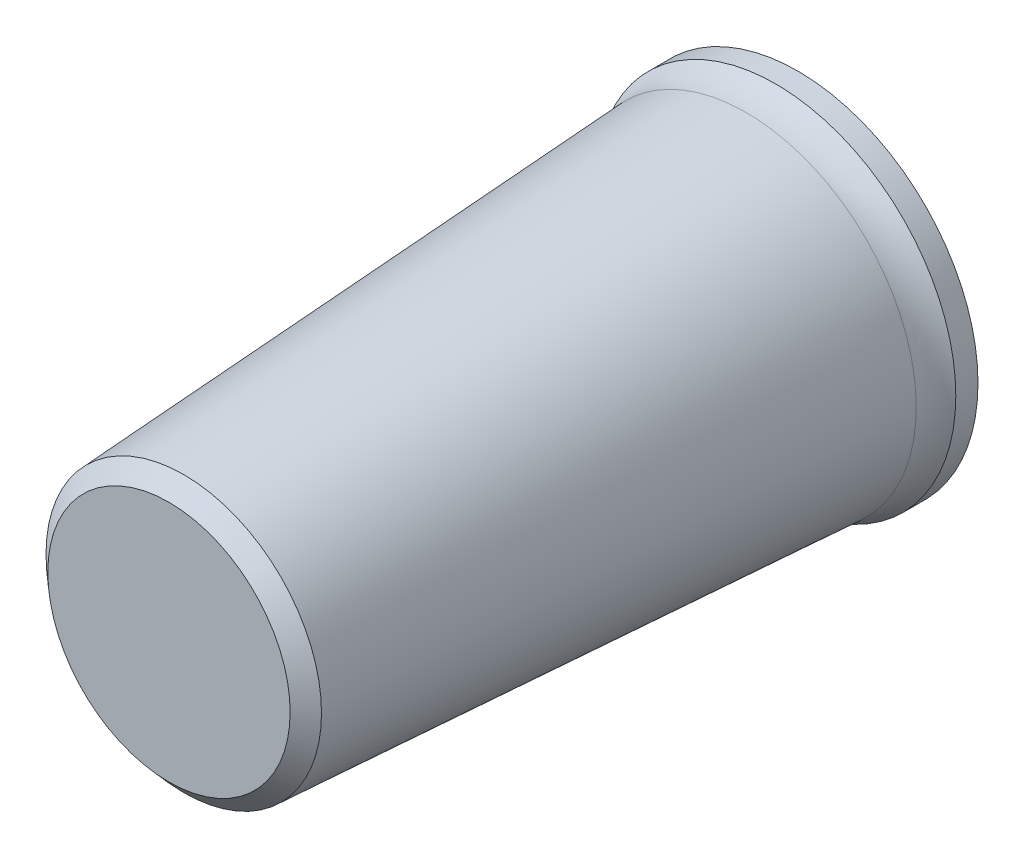
SolidWorks part; units mm, degrees
material "Polytetrafluorethylene"
ref_plane "Front Plane" through (0, 0, 0) normal (0, 0, 1) x (1, 0, 0)
ref_plane "Top Plane" through (0, 0, 0) normal (0, 1, 0) x (1, 0, 0)
ref_plane "Right Plane" through (0, 0, 0) normal (1, 0, 0) x (0, 0, -1)
ref_axis "CL" through (0, 0, 55) along (0, 0, -1)
sketch "Sketch1" plane through (0, 0, 0) normal (1, 0, 0) x (0, 0, -1)
  line L0 (-8.5, 0) -> (-0.7, 0)
  line L1 (-8.5, 0) -> (-8.5, 1.8503)
  line L2 (-8.5, 1.8503) -> (-0.7, 2.3)
  line L3 (-0.7, 2.3) -> (-0.7, 0) construction
  line L4 (-14.0337, 0) -> (14.0337, 0) construction
  line L6 (0, 2.4346) -> (0, 0)
  line L7 (0, 0) -> (-0.7, 0)
  line L8 (0, 2.4346) -> (-0.3, 2.4346)
  arc A0 (-0.7, 2.3) -> (-0.3, 2.4346) centre (-0.7461, 3.0987) ccw
  point P4 (0, 2.9154)
  point P10 (0, 0)
  point P11 (-1.288, 2.3189)
  point P14 (-0.5, 2.7448)
  dimension "D5" = 0.3
  dimension "D6" = 0.8
  dimension "D1" = 8.5
  dimension "D2" = 3.3
  dimension "D3" = 3.7005
  dimension "D4" = 4.6
  dimension "D7" = 0.4
revolve "Revolve1" add sketch "Sketch1" angle 360 about L4
chamfer "Chamfer1" distance 0.2 angle 45 1 edges at (1.8503, 0, 8.5) first distance on face at (1.8503, 0, 8.5)
